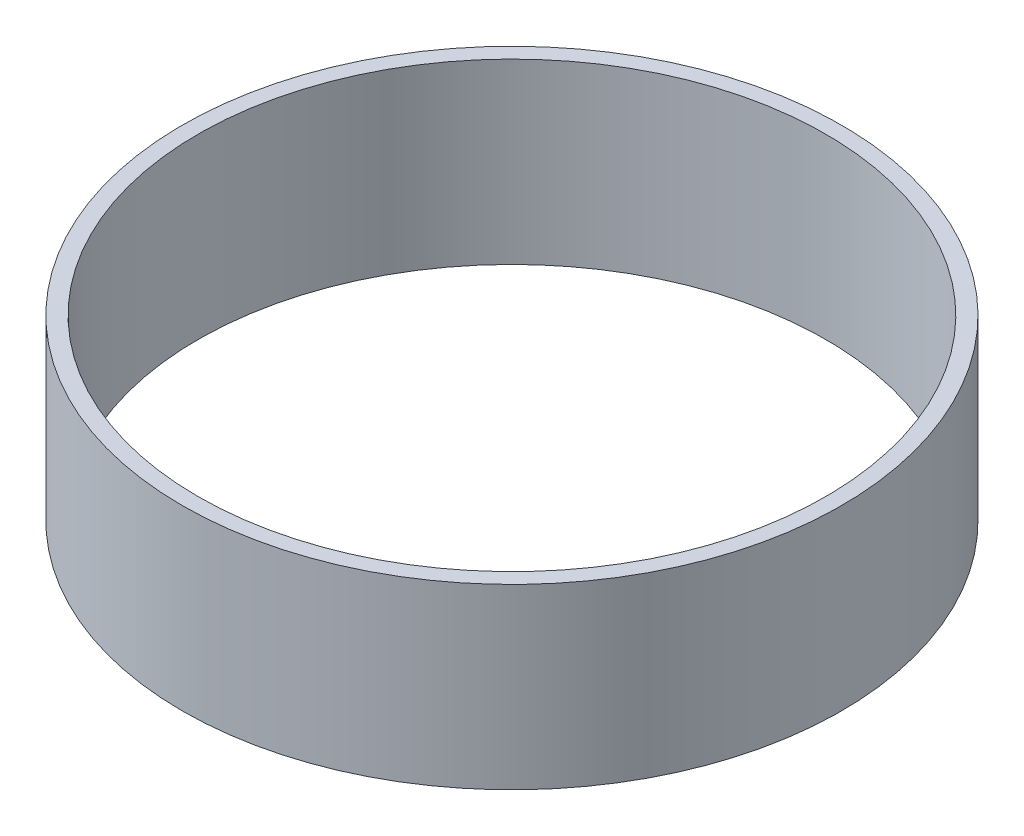
SolidWorks part; units mm, degrees
ref_plane "Спереди" through (0, 0, 0) normal (0, 0, 1) x (1, 0, 0)
ref_plane "Сверху" through (0, 0, 0) normal (0, 1, 0) x (1, 0, 0)
ref_plane "Справа" through (0, 0, 0) normal (1, 0, 0) x (0, 0, -1)
sketch "Эскиз1" plane through (0, 0, 0) normal (0, 1, 0) x (1, 0, 0)
  circle A0 centre (0, 0) radius 63
extrude "Бобышка-Вытянуть1" add sketch "Эскиз1" along normal blind 34
sketch "Эскиз2" plane through (0, 34, 0) normal (0, 1, 0) x (1, 0, 0)
  circle A0 centre (0, 0) radius 60
extrude "Вырез-Вытянуть1" cut sketch "Эскиз2" against normal blind 34
